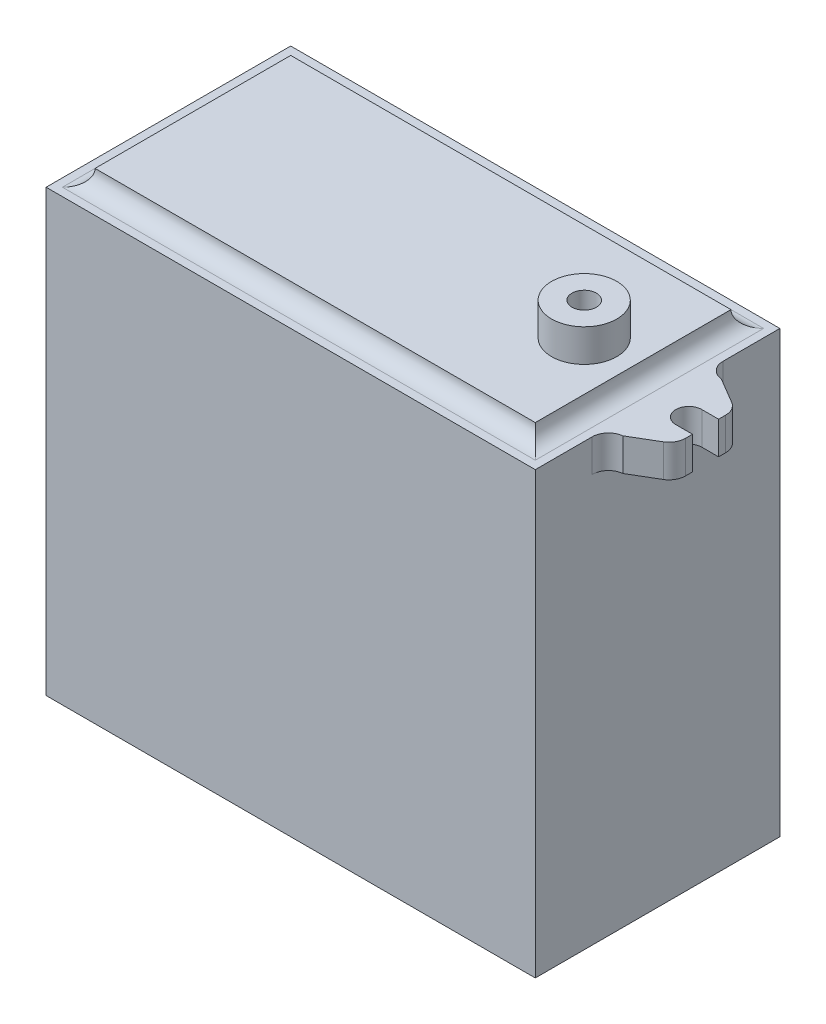
SolidWorks part; units mm, degrees
ref_plane "Front Plane" through (0, 0, 0) normal (0, 0, 1) x (1, 0, 0)
ref_plane "Top Plane" through (0, 0, 0) normal (0, 1, 0) x (1, 0, 0)
ref_plane "Right Plane" through (0, 0, 0) normal (1, 0, 0) x (0, 0, -1)
sketch "Sketch1" plane through (0, 0, 0) normal (0, 1, 0) x (1, 0, 0)
  line L0 (0.5, -40) -> (0.5, 40) construction
  line L1 (-15, 7.5) -> (15, 7.5)
  line L2 (-15, 7.5) -> (-15, -7.5)
  line L3 (-15, -7.5) -> (15, -7.5)
  line L4 (15, 7.5) -> (15, -7.5)
  line L5 (-15, 7.5) -> (15, -7.5) construction
  line L6 (-15, -7.5) -> (15, 7.5) construction
  line L7 (-25, -30.3785) -> (-25, 26.6202) construction
  point P0 (0, 0)
  dimension "D1" = 30
  dimension "D2" = 15
  dimension "D3" = 15.5
  dimension "D4" = 10
extrude "Boss-Extrude1" add sketch "Sketch1" along normal blind 27
sketch "Sketch8" plane through (0, 27, 0) normal (0, 1, 0) x (1, 0, 0)
  line L0 (15, -7.5) -> (15, 7.5) construction
  line L1 (-13.5, 6) -> (13.5, 6)
  line L2 (-13.5, 6) -> (-13.5, -6)
  line L3 (-13.5, -6) -> (13.5, -6)
  line L4 (13.5, 6) -> (13.5, -6)
  line L5 (-13.5, 6) -> (13.5, -6) construction
  line L6 (-13.5, -6) -> (13.5, 6) construction
  line L7 (15, 7.5) -> (-15, 7.5) construction
  line L8 (-15, 7.5) -> (-15, -7.5) construction
  line L9 (-15, -7.5) -> (15, -7.5) construction
  point P0 (0, 0)
  point P10 (-15, 0)
  dimension "D1" = 1.5
  dimension "D2" = 1.5
  dimension "D3" = 1.5
  dimension "D4" = 1.5
extrude "Boss-Extrude5" add sketch "Sketch8" along normal blind 1
fillet "Fillet4" radius 1 4 edges at (0, 27, 6) (13.5, 27, 0) (-13.5, 27, 0) (0, 27, -6)
sketch "Sketch9" plane through (0, 28, 0) normal (0, 1, 0) x (1, 0, 0)
  line L0 (13.5, -6) -> (13.5, 6) construction
  line L2 (13.5, 6) -> (-13.5, 6) construction
  line L3 (-13.5, -6) -> (13.5, -6) construction
  line L4 (9.85, -9.65) -> (9.85, 9.65) construction
  circle A0 centre (10.5, 0) radius 2
  dimension "D1" = 4
  dimension "D2" = 3
  dimension "D3" = 6
  dimension "D4" = 6
  dimension "D5" = 0.65
extrude "Boss-Extrude6" add sketch "Sketch9" along normal blind 2 contours A0
sketch "Sketch10" plane through (0, 30, 0) normal (0, 1, 0) x (1, 0, 0)
  circle A0 centre (10.5, 0) radius 0.75
  dimension "D1" = 1.5
extrude "Cut-Extrude2" cut sketch "Sketch10" against normal blind 2
sketch "Sketch11" plane through (0, 27, 0) normal (0, 1, 0) x (1, 0, 0)
  line L0 (-53.9521, 0) -> (62.3163, 0) construction
  line L1 (15, 3.0177) -> (15.8901, 3.0177)
  line L2 (15, -7.5) -> (15, 7.5) construction
  line L3 (15.8901, 3.0177) -> (17.9396, 1.8067)
  line L4 (17.9396, 1.8067) -> (17.9396, 0.8)
  line L5 (17.9396, 0.8) -> (16.9148, 0.8)
  line L6 (15, 3.0177) -> (15, -3.0177)
  line L7 (15, -3.0177) -> (15.8901, -3.0177)
  line L8 (15.8901, -3.0177) -> (17.9396, -1.8067)
  line L9 (17.9396, -1.8067) -> (17.9396, -0.8)
  line L10 (17.9396, -0.8) -> (16.9148, -0.8)
  arc A0 (16.9148, 0.8) -> (16.9148, -0.8) centre (16.9148, 0) ccw
  point P14 (15, 0)
extrude "Boss-Extrude7" add sketch "Sketch11" against normal blind 2 contours A0 L10 L9 L8 L7 L6 L1 L3 L4 L5
fillet "Fillet5" radius 1 4 edges at (17.9396, 26, -1.8067) (17.9396, 26, 1.8067)
